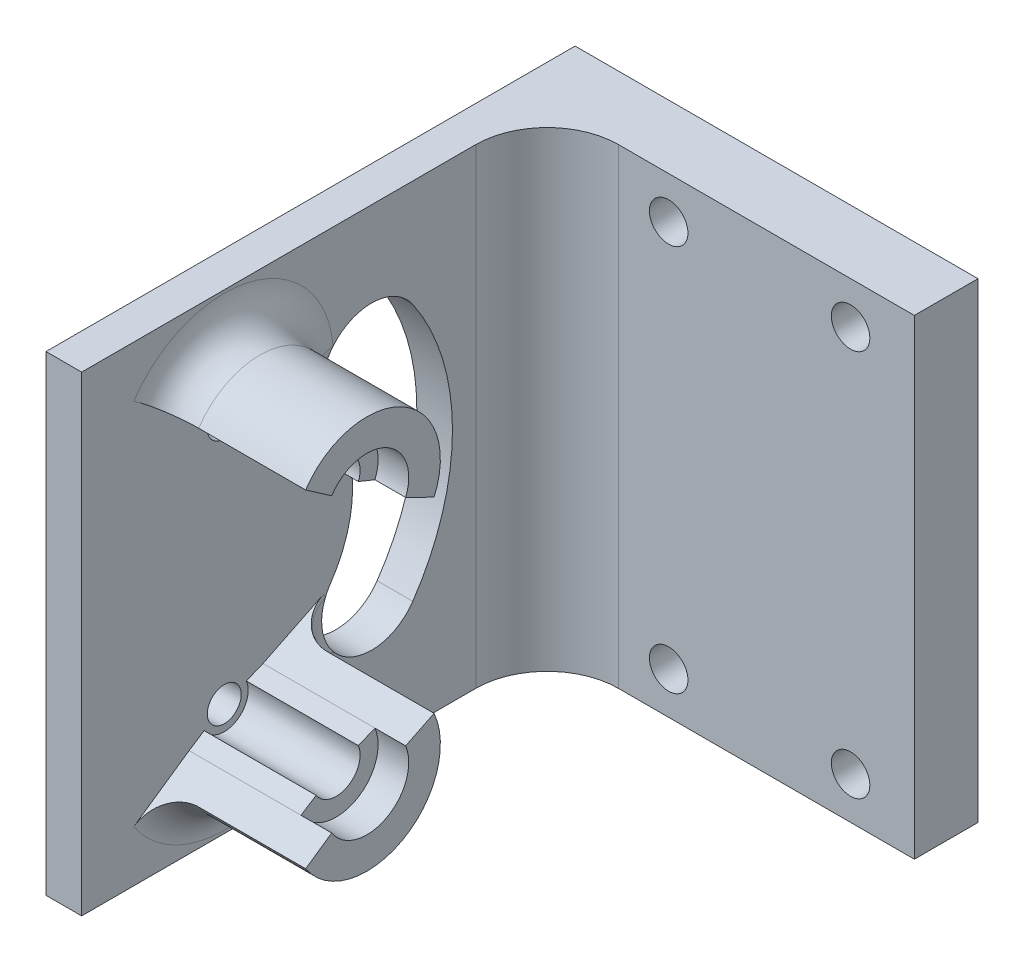
SolidWorks part; units mm, degrees
ref_plane "Front Plane" through (0, 0, 0) normal (1, 0, 0) x (0, 1, 0)
ref_plane "Top Plane" through (0, 0, 0) normal (0, 0, 1) x (0, 1, 0)
ref_plane "Right Plane" through (0, 0, 0) normal (0, 1, 0) x (-1, 0, 0)
sketch "Sketch1" plane through (0, 0, 0) normal (1, 0, 0) x (0, 1, 0)
  circle A0 centre (-28.0462, 3.137) radius 5.87
  circle A1 centre (-62.6462, 3.137) radius 5.87
  circle A2 centre (-62.6462, 3.137) radius 2.38
  circle A3 centre (-28.0462, 3.137) radius 2.38
  dimension "D2" = 11.74
  dimension "D3" = 4.76
  dimension "D1" = 34.6
sketch "Sketch2" plane through (0, 0, 0) normal (1, 0, 0) x (0, 1, 0)
  line L0 (-62.6462, 3.137) -> (-28.0462, 3.137) construction
  line L1 (-78.3695, 23.137) -> (-12.323, 23.137)
  line L2 (-78.3695, 23.137) -> (-78.3695, -51.063)
  line L3 (-78.3695, -51.063) -> (-12.323, -51.063)
  line L4 (-12.323, 23.137) -> (-12.323, -51.063)
  circle A2 centre (-62.6462, 3.137) radius 2.38 construction
  circle A3 centre (-28.0462, 3.137) radius 2.38 construction
  circle A4 centre (-62.6462, 3.137) radius 2.38
  circle A5 centre (-28.0462, 3.137) radius 2.38
  point P10 (-45.3462, 3.137)
  point P14 (-45.3462, 23.137)
  dimension "D2" = 20
  dimension "D1" = 54.2
extrude "Boss-Extrude1" add sketch "Sketch2" along normal blind 5
sketch "Sketch11" plane through (5, 0, 0) normal (1, 0, 0) x (0, 1, 0)
  line L0 (-62.6462, 3.137) -> (-28.0462, 3.137) construction
  line L1 (-60.4268, -2.2973) -> (-58.4723, -6.2848)
  line L2 (-65.8237, 8.0727) -> (-68.3465, 11.7218)
  line L3 (-45.3462, 11.0342) -> (-45.3462, -16.0572) construction
  line L4 (-30.2657, -2.2973) -> (-32.2202, -6.2848)
  line L5 (-24.8688, 8.0727) -> (-22.346, 11.7218)
  line L6 (-65.8237, 8.0727) -> (-64.4596, 5.9538)
  line L7 (-60.4268, -2.2973) -> (-61.3796, 0.0357)
  line L8 (-30.2657, -2.2973) -> (-29.3129, 0.0357)
  line L9 (-24.8688, 8.0727) -> (-26.2329, 5.9538)
  circle A4 centre (-62.6462, 3.137) radius 3.35
  circle A5 centre (-28.0462, 3.137) radius 3.35
  circle A6 centre (-62.6462, 3.137) radius 5.87 construction
  arc A8 (-68.3465, 11.7218) -> (-58.4723, -6.2848) centre (-62.6462, 3.137) ccw
  arc A9 (-65.8237, 8.0727) -> (-60.2731, -2.2319) centre (-62.6462, 3.137) ccw
  arc A10 (-24.8688, 8.0727) -> (-30.4193, -2.2319) centre (-28.0462, 3.137) cw
  arc A11 (-22.346, 11.7218) -> (-32.2202, -6.2848) centre (-28.0462, 3.137) cw
  arc A12 (-64.4596, 5.9538) -> (-61.3758, 0.0372) centre (-62.6462, 3.137) ccw
  point P5 (-45.3462, 3.137)
  point P24 (0, 0)
  dimension "D1" = 6.7
sketch "Sketch12" plane through (5, 0, 0) normal (1, 0, 0) x (0, 1, 0)
  line L0 (-62.6462, 3.137) -> (-28.0462, 3.137) construction
  line L1 (-45.3462, 3.137) -> (-45.3462, -25.9351) construction
  line L2 (-62.6462, 3.137) -> (-28.0462, 3.137) construction
  arc A0 (-59.4306, -17.518) -> (-31.2619, -17.518) centre (-45.3462, 3.137) ccw construction
  arc A1 (-63.3742, -23.3014) -> (-27.3182, -23.3014) centre (-45.3462, 3.137) ccw
  arc A2 (-55.487, -11.7346) -> (-35.2055, -11.7346) centre (-45.3462, 3.137) ccw
  arc A3 (-55.487, -11.7346) -> (-63.3742, -23.3014) centre (-59.4306, -17.518) ccw
  arc A4 (-27.3182, -23.3014) -> (-35.2055, -11.7346) centre (-31.2619, -17.518) ccw
  point P7 (-45.3462, -21.863)
  dimension "D1" = 25
  dimension "D2" = 14
extrude "Cut-Extrude2" cut sketch "Sketch12" against normal blind 10
sketch "Sketch9" plane through (5, 0, 0) normal (1, 0, 0) x (0, 1, 0)
  line L12 (-78.3695, 23.137) -> (-78.3695, -51.063) construction
  line L13 (-78.3695, -51.063) -> (-12.323, -51.063)
  line L14 (-78.3695, -51.063) -> (-78.3695, -42.138)
  line L15 (-78.3695, -42.138) -> (-12.323, -42.138)
  line L16 (-12.323, -51.063) -> (-12.323, -42.138)
  line L17 (-12.323, -51.063) -> (-12.323, 23.137) construction
  line L18 (-78.3695, -51.063) -> (-12.323, -51.063) construction
  dimension "D1" = 8.925
extrude "Boss-Extrude4" add sketch "Sketch9" along normal blind 51.5 and the other way up to surface (5 mm away) other way up to face at (0, -45.3462, -17.7187)
sketch "Sketch13" plane through (5, 0, 0) normal (1, 0, 0) x (0, 1, 0)
  line L0 (-62.6462, 3.137) -> (-28.0462, 3.137) construction
  point P4 (-45.3462, 3.137)
extrude "Boss-Extrude6" add sketch "Sketch11" along normal blind 20 contours A9 L2 A8 L1 | A11 L5 A10 L4 region at (5, -59.6633, -4.3958) region at (5, -22.6281, 0.3172)
sketch "Sketch15" plane through (5, 0, 0) normal (1, 0, 0) x (0, 1, 0)
  line L0 (-60.4268, -2.2973) -> (-58.4723, -6.2848) construction
  line L1 (-60.4268, -2.2973) -> (-61.3796, 0.0357) construction
  line L2 (-65.8237, 8.0727) -> (-64.4596, 5.9538)
  line L3 (-61.3796, 0.0357) -> (-60.4268, -2.2973)
  line L4 (-45.3462, 11.0342) -> (-45.3462, -16.0572) construction
  line L5 (-45.3462, 11.0342) -> (-45.3462, -16.0572)
  line L6 (-29.3129, 0.0357) -> (-30.2657, -2.2973)
  line L7 (-24.8688, 8.0727) -> (-26.2329, 5.9538)
  arc A0 (-65.8237, 8.0727) -> (-60.4268, -2.2973) centre (-62.6462, 3.137) ccw
  arc A1 (-64.4596, 5.9538) -> (-61.3796, 0.0357) centre (-62.6462, 3.137) ccw
  arc A2 (-26.2329, 5.9538) -> (-29.3129, 0.0357) centre (-28.0462, 3.137) cw
  arc A3 (-24.8688, 8.0727) -> (-30.2657, -2.2973) centre (-28.0462, 3.137) cw
  arc M6 (-65.8237, 8.0727) -> (-60.4268, -2.2973) centre (-62.6462, 3.137) ccw
  arc M12 (-30.2657, -2.2973) -> (-24.8688, 8.0727) centre (-28.0462, 3.137) ccw
extrude "Boss-Extrude7" add sketch "Sketch15" along normal blind 15.7 contours A1 L2 L3 M6 | L7 A2 L6 M12 region at (5, -65.2551, 6.9401) region at (5, -24.9549, 1.5281)
fillet "Fillet1" radius 10 1 edges at (5, -45.3462, -42.138)
fillet "Fillet2" radius 5 2 edges at (5, -19.0106, -1.8178) (5, -71.6818, -1.8178)
sketch "Sketch16" plane through (0, 0, -42.138) normal (0, 0, 1) x (1, 0, 0)
  line L1 (22.046, -18.1971) -> (22.046, -72.4954) construction
  line L3 (22.046, -18.1971) -> (22.046, -12.323) construction
  line L4 (15, -12.323) -> (56.5, -12.323) construction
  line L5 (22.046, -72.4954) -> (22.046, -78.3695) construction
  line L6 (15, -78.3695) -> (56.5, -78.3695) construction
  circle A0 centre (22.046, -18.1971) radius 2.7
  circle A1 centre (22.046, -72.4954) radius 2.7
  circle A2 centre (47.5567, -72.4954) radius 2.7
  circle A3 centre (47.5567, -18.1971) radius 2.7
  point P8 (22.046, -45.3462)
  dimension "D2" = 5.4
extrude "Cut-Extrude3" cut sketch "Sketch16" against normal blind 10
